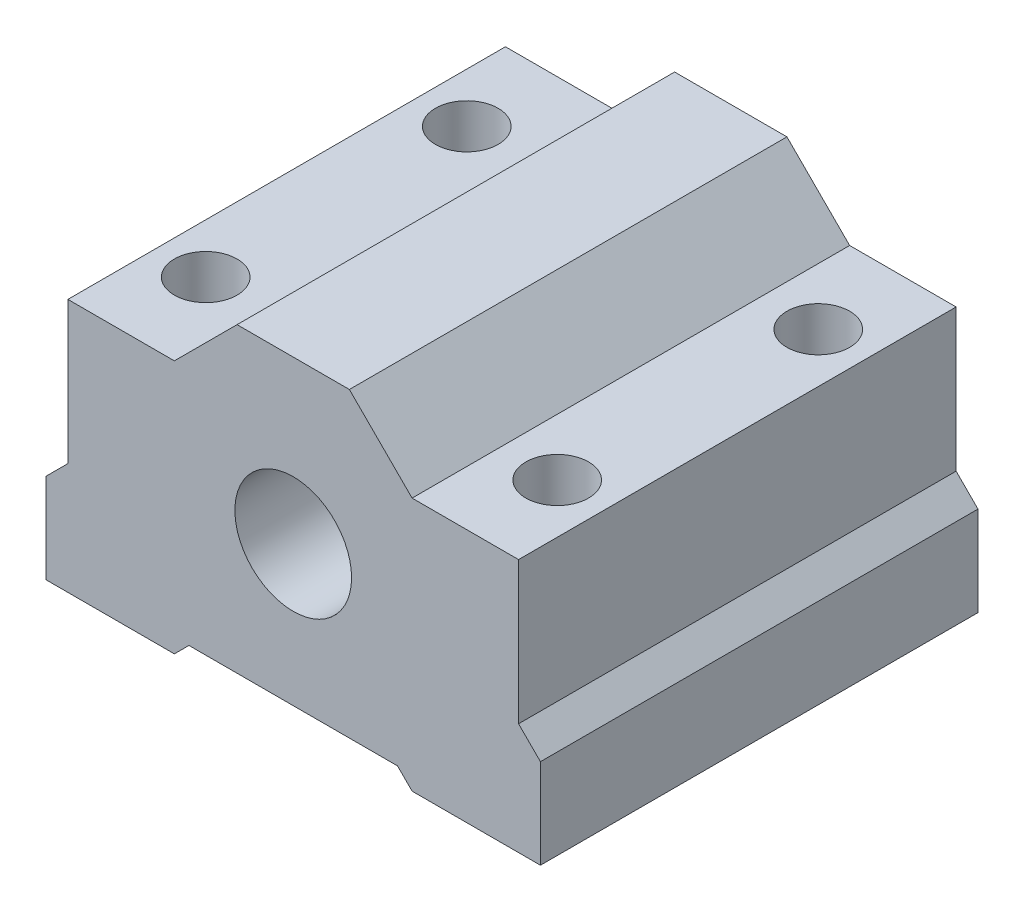
SolidWorks part; units mm, degrees
ref_plane "Front Plane" through (0, 0, 0) normal (0, 0, 1) x (1, 0, 0)
ref_plane "Top Plane" through (0, 0, 0) normal (0, 1, 0) x (1, 0, 0)
ref_plane "Right Plane" through (0, 0, 0) normal (1, 0, 0) x (0, 0, -1)
sketch "Sketch1" plane through (0, 0, 0) normal (0, 0, 1) x (1, 0, 0)
  line L0 (0, 0) -> (0, 6.15)
  line L1 (0, 6.15) -> (1.5, 7.65)
  line L2 (1.5, 7.65) -> (1.5, 17.4)
  line L3 (1.5, 17.4) -> (8.8, 17.4)
  line L4 (8.8, 17.4) -> (13.1, 21.7)
  line L5 (13.1, 21.7) -> (20.8, 21.7)
  line L6 (20.8, 21.7) -> (25.1, 17.4)
  line L7 (25.1, 17.4) -> (32.4, 17.4)
  line L8 (32.4, 17.4) -> (32.4, 7.65)
  line L9 (32.4, 7.65) -> (33.9, 6.15)
  line L10 (33.9, 6.15) -> (33.9, 0)
  line L12 (0, 0) -> (8.8, 0)
  line L13 (8.8, 0) -> (9.8, 1)
  line L14 (9.8, 1) -> (24.1, 1)
  line L15 (24.1, 1) -> (25.1, 0)
  line L16 (25.1, 0) -> (33.9, 0)
  circle A0 centre (16.95, 10.6) radius 4
  point P19 (16.95, 6.6)
  point P21 (16.95, 21.7)
  point P22 (16.95, 1)
  dimension "D9" = 8
  dimension "D1" = 33.9
  dimension "D2" = 17.4
  dimension "D3" = 45
  dimension "D4" = 7.3
  dimension "D5" = 20.7
  dimension "D6" = 4.3
  dimension "D7" = 30.9
  dimension "D8" = 7.65
  dimension "D10" = 5.6
extrude "Boss-Extrude1" add sketch "Sketch1" along normal blind 30
hole_wizard "CSK for M4 Hex Socket Countersunk Cap Screw1" positions "Sketch2" profile "Sketch4" countersink size "M4" standard "ISO" end condition through all
sketch "Sketch2" plane through (0, 0, 0) normal (0, -1, 0) x (-1, 0, 0)
  line L0 (-4.9, -6.05) -> (-4.9, -23.95) construction
  line L2 (-4.9, -6.05) -> (-29, -6.05) construction
  line L4 (-9.8, 0) -> (-24.1, 0) construction
  line L5 (0, -30) -> (0, 0) construction
  point P0 (-4.9, -6.05)
  point P2 (-4.9, -23.95)
  point P4 (-29, -6.05)
  point P6 (-29, -23.95)
  point P32 (-16.95, 0)
  point P33 (-16.95, -6.05)
  point P36 (0, -15)
  point P37 (-4.9, -15)
  dimension "D1" = 17.9
  dimension "D2" = 24.1
sketch "Sketch4" plane through (4.9, 0, 6.05) normal (1, 0, 0) x (0, 0, -1)
  line L0 (0, 0) -> (0, 21.7)
  line L1 (0, 21.7) -> (2.15, 21.7)
  line L2 (2.15, 21.7) -> (2.15, 0.83)
  line L3 (2.15, 0.83) -> (2.98, 0)
  line L5 (2.98, 0) -> (0, 0)
  line L6 (-2.15, 0.83) -> (-2.98, 0) construction
  line L11 (0, -6.35) -> (0, 107.95) construction
  dimension "Thru Hole Dia." = 4.3
  dimension "Thru Hole Depth" = 21.7
  dimension "Near C'Sink Dia." = 5.96
  dimension "Near C'Sink Angle" = 90
ref_axis "Axis1" through (29, 17.4, 6.05) along (0, -1, 0)
ref_axis "Axis2" through (4.9, 17.4, 6.05) along (0, -1, 0)
ref_plane "Plane1" through (0, 0, 6.05) normal (0, 0, 1) x (1, 0, 0)
ref_plane "Plane2" through (0, 0, 15) normal (0, 0, 1) x (1, 0, 0)
